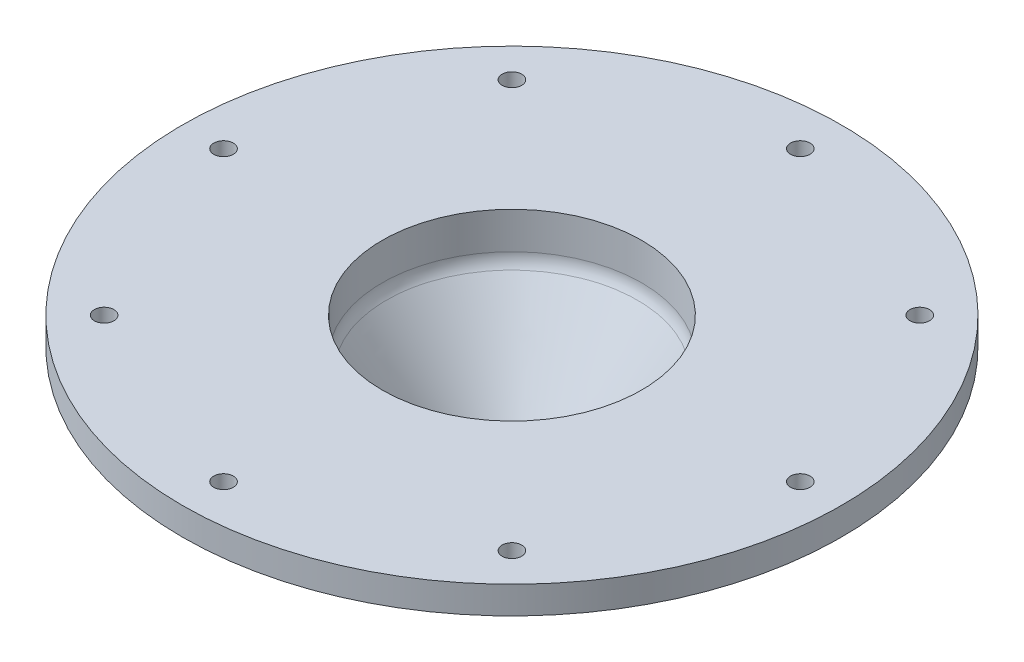
SolidWorks part; units mm, degrees
material "7075-T6 (SN)"
ref_plane "Front Plane" through (0, 0, 0) normal (0, 0, 1) x (1, 0, 0)
ref_plane "Top Plane" through (0, 0, 0) normal (0, 1, 0) x (1, 0, 0)
ref_plane "Right Plane" through (0, 0, 0) normal (1, 0, 0) x (0, 0, -1)
sketch "Sketch1" plane through (0, 0, 0) normal (0, 1, 0) x (1, 0, 0)
  circle A0 centre (0, 0) radius 38.1
  dimension "D1" = 76.2
extrude "Boss-Extrude1" add sketch "Sketch1" along normal blind 3.175
hole_wizard "Tap Drill for #4-40 Tap1" positions "Sketch3" profile "Sketch4" hole size "#4-40" standard "ANSI Inch" end condition through all
sketch "Sketch3" plane through (0, 0, 0) normal (0, -1, 0) x (-1, 0, 0)
  point P0 (0, -33.3375)
  dimension "D1" = 33.3375
sketch "Sketch4" plane through (0, 0, 33.3375) normal (1, 0, 0) x (0, 0, -1)
  line L0 (0, 0) -> (0, 3.175)
  line L1 (0, 3.175) -> (1.1303, 3.175)
  line L2 (1.1303, 3.175) -> (1.1303, 0)
  line L5 (1.1303, 0) -> (0, 0)
  line L11 (0, -6.35) -> (0, 107.95) construction
  dimension "Thru Hole Dia." = 2.2606
  dimension "Thru Hole Depth" = 3.175
pattern_circular "CirPattern1" count 8 over 360 about axis through (0, 0, 0) along (0, 1, 0) of "Tap Drill for #4-40 Tap1"
sketch "Sketch5" plane through (0, 0, 0) normal (0, -1, 0) x (1, 0, 0)
  circle A0 centre (0, 0) radius 25.4
  dimension "D1" = 50.8
extrude "Boss-Extrude2" add sketch "Sketch5" along normal blind 19.05
sketch "Sketch6" plane through (0, -19.05, 0) normal (0, -1, 0) x (1, 0, 0)
  circle A0 centre (0, 0) radius 5
  dimension "D1" = 10
extrude "Cut-Extrude1" cut sketch "Sketch6" against normal through all both and the other way through all
sketch "Sketch7" plane through (0, 3.175, 0) normal (0, 1, 0) x (1, 0, 0)
  circle A0 centre (0, 0) radius 15
  dimension "D1" = 30
extrude "Cut-Extrude2" cut sketch "Sketch7" against normal blind 5.08
sketch "Sketch8" plane through (0, -1.905, 0) normal (0, 1, 0) x (1, 0, 0)
  circle A0 centre (0, 0) radius 15
  circle A1 centre (0, 0) radius 15 construction
  dimension "D1" = 0
ref_plane "Plane1" through (0, -15.875, 0) normal (0, -1, 0) x (-1, 0, 0)
sketch "Sketch9" plane through (0, -15.875, 0) normal (0, -1, 0) x (-1, 0, 0)
  circle A0 centre (0, 0) radius 5
  circle A1 centre (0, 0) radius 5 construction
  dimension "D1" = 0
loft "Cut-Loft1" cut profiles "Sketch8", "Sketch9" connector at (0, -1.905, 15) connector at (-1.3659, -15.875, 4.8098)
sketch "Sketch10" plane through (0, 0, 0) normal (0, 0, 1) x (1, 0, 0)
  line L6 (0, 0) -> (0, -33.2378) construction
  line L7 (-25.4, 0) -> (-24.4, 0)
  line L8 (-25.4, 0) -> (25.4, 0) construction
  line L9 (-24.4, 0) -> (-8.4152, -19.05)
  line L10 (-25.4, -19.05) -> (25.4, -19.05) construction
  line L11 (-8.4152, -19.05) -> (-25.4, -19.05)
  line L12 (-25.4, -19.05) -> (-25.4, 0)
  dimension "D1" = 50
  dimension "D2" = 1
revolve "Cut-Revolve1" cut sketch "Sketch10" angle 360 about L6
fillet "Fillet2" radius 2.54 1 edges at (0, -1.905, 15)
